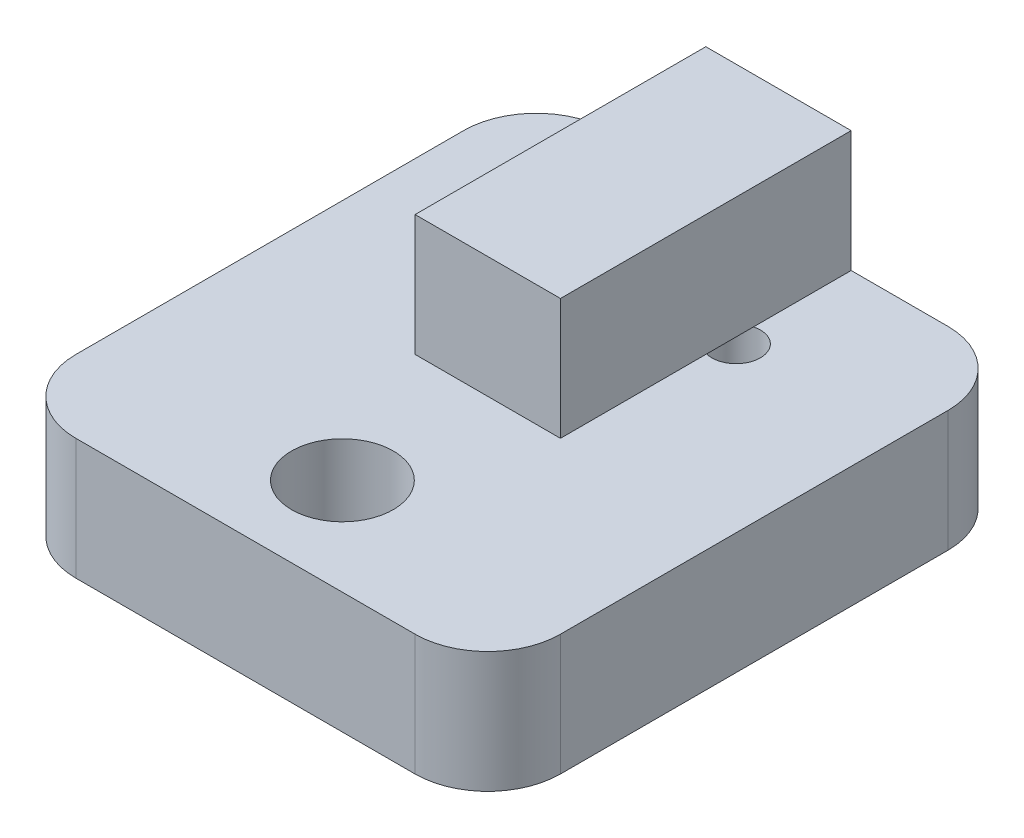
SolidWorks part; units mm, degrees
ref_plane "前视基准面" through (0, 0, 0) normal (0, 0, 1) x (1, 0, 0)
ref_plane "上视基准面" through (0, 0, 0) normal (0, 1, 0) x (1, 0, 0)
ref_plane "右视基准面" through (0, 0, 0) normal (1, 0, 0) x (0, 0, -1)
sketch "草图1" plane through (0, 0, 0) normal (0, 1, 0) x (1, 0, 0)
  line L0 (10, 31.5863) -> (10, -15.5509) construction
  line L1 (0, 0) -> (20, 0)
  line L2 (0, 0) -> (0, 22)
  line L3 (0, 22) -> (20, 22)
  line L4 (20, 0) -> (20, 22)
  line L5 (-9.9752, 10) -> (35.1948, 10) construction
  line L7 (7, 22) -> (13, 22)
  line L8 (7, 22) -> (7, 10)
  line L9 (7, 10) -> (13, 10)
  line L10 (13, 22) -> (13, 10)
  line L11 (7, 22) -> (13, 10) construction
  line L12 (7, 10) -> (13, 22) construction
  circle A0 centre (10, 4) radius 2.1
  circle A1 centre (6.75, 17) radius 1
  circle A2 centre (13.25, 17) radius 1
  point P11 (10, 16)
  dimension "D7" = 4.2
  dimension "D11" = 2
  dimension "D1" = 20
  dimension "D2" = 22
  dimension "D3" = 6
  dimension "D4" = 10
  dimension "D5" = 12
  dimension "D6" = 12
  dimension "D8" = 4
  dimension "D9" = 5
  dimension "D10" = 3.25
extrude "凸台-拉伸1" add sketch "草图1" along normal blind 5 contours L10 A2 L9 L8 A1 L3 L2 L1 L4 A0 | L10 A2 L3 L8 A1 L9 region at (0.2973, 0, -11) region at (10, 0, -15.9692)
extrude "凸台-拉伸2" add sketch "草图1<3>" along normal blind 5 from vertex contours L10 A2 L3 L8 A1 L9 | A2 L10 | L8 A1 region at (10, 0, -15.9692) region at (7.3124, 0, -17) region at (12.6876, 0, -17) starting at point (20, 5, -22)
sketch "草图1<3>" plane through (0, 0, 0) normal (0, 1, 0) x (1, 0, 0) same geometry as "草图1"
fillet "圆角2" radius 3 4 edges at (20, 2.5, 0) (0, 2.5, 0) (0, 2.5, -22) (20, 2.5, -22)
